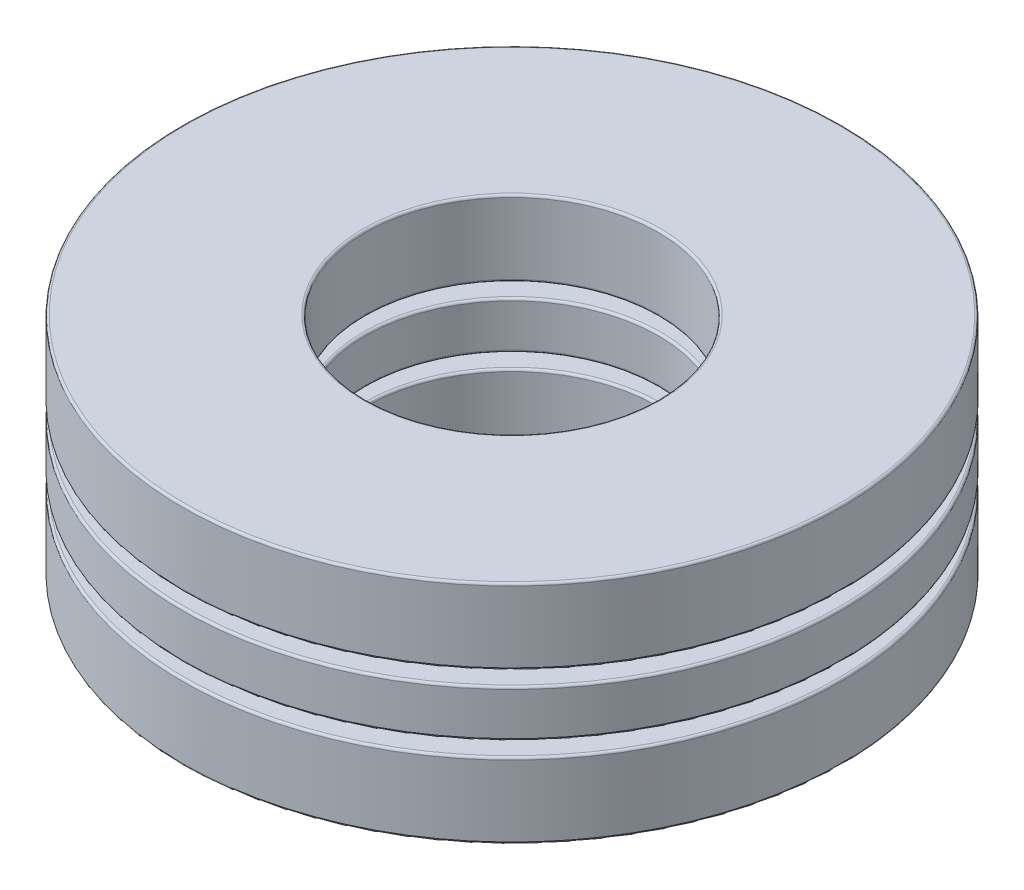
SolidWorks part; units mm, degrees
ref_plane "Front Plane" through (0, 0, 0) normal (0, 0, 1) x (1, 0, 0)
ref_plane "Top Plane" through (0, 0, 0) normal (0, 1, 0) x (1, 0, 0)
ref_plane "Right Plane" through (0, 0, 0) normal (1, 0, 0) x (0, 0, -1)
sketch "Sketch1" plane through (0, 0, 0) normal (1, 0, 0) x (0, 0, -1)
  line L0 (-7.1438, 0) -> (7.1438, 0) construction
  line L1 (0, -2.4511) -> (0, 2.4511) construction
  line L2 (-7.1438, 0.5106) -> (-3.175, 0.5106)
  line L3 (-7.1438, 0.5106) -> (-7.1438, -0.5106)
  line L4 (-7.1438, -0.5106) -> (-3.175, -0.5106)
  line L5 (-3.175, 0.5106) -> (-3.175, -0.5106)
  line L6 (-5.1594, 0.817) -> (-5.1594, -0.817) construction
  circle A0 centre (-5.1594, 0) radius 0.817 construction
  point P13 (-5.1594, 0.5106)
  dimension "OD" = 14.2875
  dimension "Shaft Dia" = 6.35
  dimension "Th" = 4.9022
  dimension "D1" = 1.6341
  dimension "D2" = 1.0213
revolve "Revolve1" add sketch "Sketch1" angle 360 about L1
sketch "Sketch3" plane through (0, 0, 0) normal (1, 0, 0) x (0, 0, -1)
  line L0 (-5.1594, 0.817) -> (-5.1594, -0.817)
  arc A0 (-5.1594, 0.817) -> (-5.1594, -0.817) centre (-5.1594, 0) ccw
  circle A1 centre (-5.1594, 0) radius 0.817 construction
revolve "Cut-Revolve1" cut sketch "Sketch3" angle 360 about L0
sketch "Sketch2" plane through (0, 0, 0) normal (1, 0, 0) x (0, 0, -1)
  line L0 (-5.1594, 0.817) -> (-5.1594, -0.817)
  arc A0 (-5.1594, 0.817) -> (-5.1594, -0.817) centre (-5.1594, 0) ccw
  circle A2 centre (-5.1594, 0) radius 0.817 construction
revolve "Revolve2" add sketch "Sketch2" angle 360 about L0
ref_axis "Axis1" through (0, 2.4511, 0) along (0, -1, 0)
pattern_circular "CirPattern1" count 7 every 51.429 about axis through (0, 2.4511, 0) along (0, -1, 0) of bodies 187
pattern_circular "CirPattern2" count 7 every 51.429 about axis through (0, 2.4511, 0) along (0, -1, 0) of "Cut-Revolve1"
sketch "Sketch4" plane through (0, 0, 0) normal (1, 0, 0) x (0, 0, -1)
  line L0 (-7.1438, 0.5106) -> (-7.1438, -0.5106) construction
  line L1 (-7.1438, 0.817) -> (-3.175, 0.817)
  line L2 (-7.1438, 0.817) -> (-7.1438, 2.4511)
  line L3 (-7.1438, 2.4511) -> (-3.175, 2.4511)
  line L4 (-3.175, 0.817) -> (-3.175, 2.4511)
  line L5 (-7.1438, -2.4511) -> (-3.175, -2.4511)
  line L6 (-7.1438, -2.4511) -> (-7.1438, -0.817)
  line L7 (-7.1438, -0.817) -> (-3.175, -0.817)
  line L8 (-3.175, -2.4511) -> (-3.175, -0.817)
  line L9 (-5.1594, 0.817) -> (-5.1594, -0.817) construction
  line L10 (-3.175, 0.5106) -> (-3.175, -0.5106) construction
  line L11 (0, 0) -> (-7.1438, 0) construction
  line L12 (-7.1438, 0) -> (7.1438, 0) construction
  dimension "Ht" = 4.9022
revolve "Revolve3" add sketch "Sketch4" angle 360 about L1
fillet "Fillet1" radius 0.049 4 edges at (0, 0.817, -3.175) (0, 2.4511, -3.175) (0, 0.817, -7.1438) (0, 2.4511, -7.1438)
fillet "Fillet2" radius 0.049 4 edges at (0, -0.5106, -3.175) (0, 0.5106, -3.175) (0, -0.5106, -7.1438) (0, 0.5106, -7.1438)
fillet "Fillet3" radius 0.049 4 edges at (0, -2.4511, -3.175) (0, -0.817, -3.175) (0, -2.4511, -7.1438) (0, -0.817, -7.1438)
equation "\"D1@Sketch1\" = \"Th@Sketch1\"/3"
equation "\"D2@Sketch1\" = \"D1@Sketch1\"*.625"
equation "\"Balls@CirPattern1\" = \"OD@Sketch1\"*12"
equation "\"Angle@CirPattern1\" = 360/\"Balls@CirPattern1\""
equation "\"D1@CirPattern2\" = \"Balls@CirPattern1\""
equation "\"D2@CirPattern2\" = \"Angle@CirPattern1\""
equation "\"D1@Fillet1\" = \"Th@Sketch1\"*.01"
equation "\"D1@Fillet2\" = \"D1@Fillet1\""
equation "\"D1@Fillet3\" = \"D1@Fillet1\""
